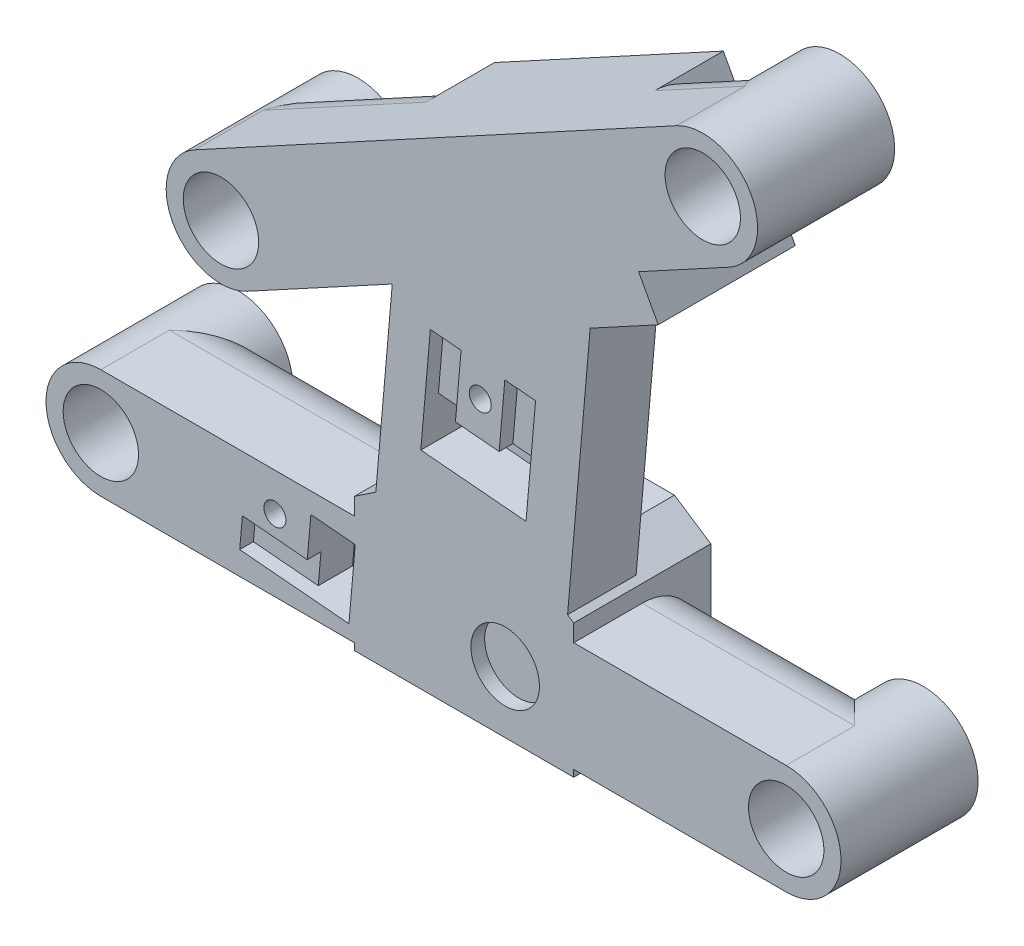
SolidWorks part; units mm, degrees
ref_plane "Front Plane" through (0, 0, 0) normal (0, 0, 1) x (1, 0, 0)
ref_plane "Top Plane" through (0, 0, 0) normal (0, 1, 0) x (1, 0, 0)
ref_plane "Right Plane" through (0, 0, 0) normal (1, 0, 0) x (0, 0, -1)
sketch "Sketch1" plane through (0, 0, 0) normal (0, 0, 1) x (1, 0, 0)
  line L0 (0, 0) -> (32, 0)
  line L1 (32, 0) -> (32, 19.5)
  line L2 (32, 19.5) -> (26.7, 23)
  line L3 (26.7, 23) -> (5.2, 23)
  line L4 (5.2, 23) -> (0, 19.5)
  line L5 (0, 19.5) -> (0, 0)
  dimension "D1" = 32
  dimension "D2" = 19.5
  dimension "D3" = 21.5
  dimension "D4" = 23
  dimension "D5" = 26.8
extrude "Boss-Extrude1" add sketch "Sketch1" along normal blind 20
sketch "Sketch2" plane through (0, 0, 0) normal (0, 0, -1) x (-1, 0, 0)
  line L0 (0, 0) -> (88.9399, 0) construction
  line L1 (88.9399, 0) -> (-120.0605, 0) construction
  line L2 (-32, 0) -> (-32, 19.5) construction
  line L3 (0, 19.5) -> (0, 0) construction
  circle A0 centre (-63, 9) radius 5.5
  circle A1 centre (-63, 9) radius 8
  circle A2 centre (37, 9) radius 5.5
  circle A3 centre (37, 9) radius 8
  dimension "D1" = 11
  dimension "D2" = 16
  dimension "D5" = 11
  dimension "D6" = 16
  dimension "D3" = 9
  dimension "D4" = 31
  dimension "D7" = 9
  dimension "D8" = 37
extrude "Boss-Extrude2" add sketch "Sketch2" against normal blind 20 separate body
sketch "Sketch4" plane through (32, 0, 0) normal (1, 0, 0) x (0, 0, -1)
  line L0 (0, 0) -> (0, 19.5) construction
  line L1 (0, 17) -> (-18, 17)
  line L2 (0, 17) -> (0, 1)
  line L3 (0, 1) -> (-18, 1)
  line L4 (-18, 17) -> (-18, 1)
  line L5 (-20, 19.5) -> (0, 19.5) construction
  dimension "D1" = 18
  dimension "D2" = 16
  dimension "D3" = 2.5
extrude "Boss-Extrude3" add sketch "Sketch4" along normal up to surface (31 mm away) up to face at (55, 9, 20)
sketch "Sketch5" plane through (0, 0, 0) normal (-1, 0, 0) x (0, 0, 1)
  line L0 (0, 19.5) -> (0, 0) construction
  line L1 (0, 17) -> (18, 17)
  line L2 (0, 17) -> (0, 1)
  line L3 (0, 1) -> (18, 1)
  line L4 (18, 17) -> (18, 1)
  line L5 (20, 19.5) -> (0, 19.5) construction
  dimension "D1" = 2.5
  dimension "D2" = 18
  dimension "D3" = 16
extrude "Boss-Extrude4" add sketch "Sketch5" along normal up to surface (37 mm away) up to face at (-45, 9, 20)
sketch "Sketch6" plane through (0, 0, 0) normal (0, 0, -1) x (-1, 0, 0)
  line L0 (-31.1, 20.0943) -> (-34.4, 57.9508)
  line L1 (-32, 19.5) -> (-26.7, 23) construction
  line L2 (-3.1254, 21.6036) -> (-5.9785, 54.3336)
  line L3 (-5.2, 23) -> (0, 19.5) construction
  line L4 (-10.9396, 45.2033) -> (-44.3289, 63.3458)
  line L5 (-44.3289, 63.3458) -> (-33.8254, 82.6765)
  line L6 (-33.8254, 82.6765) -> (-0.436, 64.5339)
  line L7 (-0.436, 64.5339) -> (-10.9396, 45.2033)
  line L8 (-32, 17) -> (-32, 19.5) construction
  line M11 (0, 19.5) -> (-5.2, 23)
  line M12 (-5.2, 23) -> (-26.7, 23)
  line M13 (-26.7, 23) -> (-32, 19.5)
  dimension "D1" = 28
  dimension "D2" = 0.9
  dimension "D3" = 38
  dimension "D4" = 2.4
  dimension "D5" = 38
  dimension "D6" = 22
  dimension "D7" = 123.5
  dimension "D8" = 11.3
extrude "Boss-Extrude5" add sketch "Sketch6" against normal blind 10 contours L2 L7 L4 L0 M13 M12 M11 region at (19.3948, 37.1745, 0)
extrude "Boss-Extrude6" add sketch "Sketch6<3>" against normal blind 20 contours L7 L6 L5 L4 region at (22.3825, 63.9399, 0)
sketch "Sketch6<3>" plane through (0, 0, 0) normal (0, 0, -1) x (-1, 0, 0) same geometry as "Sketch6"
sketch "Sketch7" plane through (0, 0, 20) normal (0, 0, 1) x (1, 0, 0)
  line L0 (-19.4685, 44.6138) -> (50.8248, 82.8087) construction
  line L3 (33.8254, 82.6765) -> (0.436, 64.5339) construction
  line L4 (0.436, 64.5339) -> (10.9396, 45.2033) construction
  line L6 (44.3289, 63.3458) -> (33.8254, 82.6765) construction
  circle A0 centre (50.8248, 82.8087) radius 5.5
  circle A1 centre (50.8248, 82.8087) radius 8
  circle A2 centre (-19.4685, 44.6138) radius 5.5
  circle A3 centre (-19.4685, 44.6138) radius 8
  dimension "D4" = 11
  dimension "D5" = 16
  dimension "D6" = 11
  dimension "D7" = 16
  dimension "D1" = 8
  dimension "D2" = 27
  dimension "D3" = 15
extrude "Boss-Extrude7" add sketch "Sketch7" against normal blind 20 separate body
sketch "Sketch8" plane through (27.409, 14.8931, 0) normal (-0.8787, -0.4774, 0) x (0, 0, 1)
  line L0 (0, 56.4956) -> (0, 44.8868) construction
  line L1 (0, 56.4956) -> (18, 56.4956)
  line L2 (0, 56.4956) -> (0, 40.4956)
  line L3 (0, 40.4956) -> (18, 40.4956)
  line L4 (18, 56.4956) -> (18, 40.4956)
  line L6 (20, 56.4956) -> (0, 56.4956) construction
  dimension "D2" = 16
  dimension "D3" = 18
extrude "Boss-Extrude8" add sketch "Sketch8" along normal up to surface (27 mm away) up to face at (-11.4685, 44.6138, 0)
sketch "Sketch9" plane through (60.7984, 33.0356, 0) normal (0.8787, 0.4774, 0) x (0, 0, -1)
  line L1 (0, 56.4956) -> (-18, 56.4956)
  line L2 (0, 56.4956) -> (0, 40.4956)
  line L3 (0, 40.4956) -> (-18, 40.4956)
  line L4 (-18, 56.4956) -> (-18, 40.4956)
  dimension "D1" = 18
  dimension "D2" = 16
extrude "Boss-Extrude9" add sketch "Sketch9" along normal up to surface (15 mm away) up to face at (58.8248, 82.8087, 0)
fillet "Fillet1" radius 8 8 edges at (47.5, 1, 18) (47.5, 17, 18) (48.0543, 72.1986, 18) (40.4154, 86.2572, 18) (-11.426, 58.0885, 18) (-3.787, 44.0299, 18) (-18.5, 1, 18) (-18.5, 17, 18)
sketch "Sketch10" plane through (0, 0, 20) normal (0, 0, 1) x (1, 0, 0)
  line L0 (9.0299, 48.7179) -> (42.4192, 66.8605)
  line L1 (0.436, 64.5339) -> (10.9396, 45.2033) construction
  line L2 (44.3289, 63.3458) -> (33.8254, 82.6765) construction
  line L3 (42.4192, 66.8605) -> (41.4643, 68.6178)
  line L4 (41.4643, 68.6178) -> (8.075, 50.4753)
  line L5 (8.075, 50.4753) -> (10.9396, 45.2033) construction
  line L6 (8.075, 50.4753) -> (9.0299, 48.7179)
  line L8 (10.9396, 45.2033) -> (44.3289, 63.3458) construction
  dimension "D1" = 2
  dimension "D2" = 4
extrude "Cut-Extrude1" cut sketch "Sketch10" against normal blind 1
sketch "Sketch11" plane through (0, 0, 20) normal (0, 0, 1) x (1, 0, 0)
  line L0 (18.9906, 10.8834) -> (18.6, 6.3)
  line L1 (18.6, 6.3) -> (8.0383, 7.2)
  line L2 (8.0383, 7.2) -> (8.4288, 11.7834)
  line L3 (8.4288, 11.7834) -> (18.9906, 10.8834)
  line L4 (0, 0) -> (32, 0) construction
  line L5 (32, 0) -> (32, 19.5) construction
  dimension "D1" = 10.6
  dimension "D2" = 4.6
  dimension "D3" = 6.3
  dimension "D4" = 7.2
  dimension "D5" = 13.4
extrude "Boss-Extrude10" add sketch "Sketch11" along normal blind 2.8
sketch "Sketch12" plane through (0, 0, 0) normal (0, 0, -1) x (-1, 0, 0)
  line L0 (-31.1, 20.0943) -> (-3.2058, 22.5259) construction
  line L1 (-3.1254, 21.6036) -> (-5.5212, 49.0876) construction
  line L2 (-25.0378, 28.8539) -> (-9.6901, 30.1918)
  line L3 (-9.6901, 30.1918) -> (-11.0796, 46.1313)
  line L4 (-11.0796, 46.1313) -> (-15.5626, 45.7405)
  line L5 (-15.5626, 45.7405) -> (-14.7376, 36.2764)
  line L6 (-14.7376, 36.2764) -> (-21.1193, 35.7201)
  line L7 (-21.1193, 35.7201) -> (-21.9443, 45.1842)
  line L8 (-21.9443, 45.1842) -> (-26.4273, 44.7934)
  line L9 (-26.4273, 44.7934) -> (-25.0378, 28.8539)
  line L10 (-25.6023, 35.3293) -> (-10.2546, 36.6672)
  line L11 (-31.1, 20.0943) -> (-34.4, 57.9508) construction
  line L12 (-17.9284, 35.9983) -> (-19.3449, 52.248) construction
  line L13 (0, 0) -> (-32, 0) construction
  line L14 (-32, 0) -> (-32, 1) construction
  line L15 (-0.1188, 13.4597) -> (0.8, 3)
  line L16 (0.8, 3) -> (16.7386, 4.4)
  line L17 (16.7386, 4.4) -> (16.3449, 8.8827)
  line L18 (16.3449, 8.8827) -> (6.8813, 8.0515)
  line L19 (6.8813, 8.0515) -> (6.3563, 14.0285)
  line L20 (6.3563, 14.0285) -> (-0.1188, 13.4597)
  line L21 (6.8813, 8.0515) -> (7.2751, 3.5688)
  line L22 (37, 1) -> (0, 1) construction
  line L23 (0, 1) -> (0, 0) construction
  line L24 (6.8813, 8.0515) -> (7.2751, 3.5688)
  circle A0 centre (-18.3626, 40.9794) radius 1.6
  circle A1 centre (-22, 9) radius 5
  circle A2 centre (11.5996, 11.4775) radius 1.605
  dimension "D7" = 3.2
  dimension "D9" = 10
  dimension "D12" = 3.21
  dimension "D1" = 8.2
  dimension "D2" = 6.8
  dimension "D3" = 5.7941
  dimension "D4" = 4.5
  dimension "D5" = 16
  dimension "D6" = 9.5
  dimension "D8" = 5
  dimension "D10" = 9
  dimension "D11" = 10
  dimension "D13" = 16
  dimension "D14" = 10.5
  dimension "D15" = 6.5
  dimension "D16" = 6
  dimension "D17" = 3
  dimension "D18" = 5
  dimension "D19" = 2
  dimension "D20" = 0.8
  dimension "D21" = 3.4
extrude "Cut-Extrude2" cut sketch "Sketch12" against normal blind 2 contours A1 region at (22, 9, 0)
extrude "Cut-Extrude3" cut sketch "Sketch12<4>" against normal blind 7 contours L21 L19 L20 L15 L16 | L10 L9 L2 L3 L6 region at (17.6462, 32.7605, 0) region at (-3.5782, 8.5142, 0)
sketch "Sketch12<4>" plane through (0, 0, 0) normal (0, 0, -1) x (-1, 0, 0) same geometry as "Sketch12"
extrude "Cut-Extrude4" cut sketch "Sketch12<6>" against normal blind 2 contours L18 L21 L16 L17 | L5 L10 L3 L4 | L9 L10 L7 L8 region at (23.7733, 40.2568, 0) region at (12.9086, 41.2039, 0) region at (-11.81, 6.2257, 0)
sketch "Sketch12<6>" plane through (0, 0, 0) normal (0, 0, -1) x (-1, 0, 0) same geometry as "Sketch12"
extrude "Cut-Extrude5" cut sketch "Sketch12<7>" against normal blind 8 contours A2 | A0 region at (18.3626, 40.9794, 0) region at (-11.5996, 11.4775, 0)
sketch "Sketch12<7>" plane through (0, 0, 0) normal (0, 0, -1) x (-1, 0, 0) same geometry as "Sketch12"
sketch "Sketch13" plane through (1.2328, -0.1075, 0) normal (-0.9962, 0.0868, 0) x (0, 0, 1)
  line L0 (0, 21.7934) -> (0, 49.3816) construction
  line L1 (4.2, 45.2934) -> (7, 45.2934)
  line L2 (4.2, 45.2934) -> (4.2, 39.4934)
  line L3 (4.2, 39.4934) -> (7, 39.4934)
  line L4 (7, 45.2934) -> (7, 39.4934)
  line L5 (10, 21.7934) -> (0, 21.7934) construction
  dimension "D1" = 5.8
  dimension "D2" = 2.8
  dimension "D3" = 4.2
  dimension "D4" = 17.7
extrude "Cut-Extrude6" cut sketch "Sketch13" against normal blind 22
sketch "Sketch14" plane through (0, 1, 0) normal (0, -1, 0) x (1, 0, 0)
  line L0 (0, 0) -> (0, 10) construction
  line L1 (-15.4, 7) -> (-9.6, 7)
  line L2 (-15.4, 7) -> (-15.4, 4.2)
  line L3 (-15.4, 4.2) -> (-9.6, 4.2)
  line L4 (-9.6, 7) -> (-9.6, 4.2)
  line L5 (-37, 0) -> (0, 0) construction
  dimension "D1" = 5.8
  dimension "D2" = 2.8
  dimension "D3" = 9.6
  dimension "D4" = 4.2
extrude "Cut-Extrude7" cut sketch "Sketch14" against normal blind 14.5
mirror "Mirror8" about plane through (50.8248, 82.8087, 0) normal (0, 0, 1) of "Boss-Extrude1"
mirror "Mirror10" about plane through (50.8248, 82.8087, 0) normal (0, 0, 1) of "Boss-Extrude3", "Boss-Extrude4", "Boss-Extrude5", "Boss-Extrude6", "Boss-Extrude8", "Boss-Extrude9", "Fillet1", "Cut-Extrude1", "Boss-Extrude10", "Cut-Extrude2", "Cut-Extrude3", "Cut-Extrude4", "Cut-Extrude5", "Cut-Extrude6", "Cut-Extrude7"
sketch "Sketch15" plane through (0, 0, 0) normal (0, 0, -1) x (-1, 0, 0)
  circle A0 centre (-50.8248, 82.8087) radius 5.5
  circle A1 centre (-50.8248, 82.8087) radius 8
  circle A2 centre (19.4685, 44.6138) radius 5.5
  circle A3 centre (19.4685, 44.6138) radius 8
  circle A4 centre (37, 9) radius 5.5
  circle A5 centre (37, 9) radius 8
  circle A6 centre (-63, 9) radius 5.5
  circle A7 centre (-63, 9) radius 8
  dimension "D1" = 11
  dimension "D2" = 16
extrude "Boss-Extrude11" add sketch "Sketch15" along normal blind 20
sketch "Sketch16" plane through (-26.973, 49.6409, 0) normal (-0.4774, 0.8787, 0) x (0.8787, 0.4774, 0)
  line L0 (0, 0) -> (-59.1276, 0)
  line L1 (-59.1276, 0) -> (-59.1276, -32.6264)
  line L2 (-59.1276, -32.6264) -> (114.1765, -32.6264)
  line L3 (114.1765, -32.6264) -> (114.1765, 0)
  line L4 (114.1765, 0) -> (0, 0)
extrude "Cut-Extrude8" cut sketch "Sketch16" against normal through all both and the other way through all
sketch "Sketch17" plane through (0, 1, 0) normal (0, -1, 0) x (1, 0, 0)
  line L0 (-9.6, -4.2) -> (-8.1, -4.2)
  line L1 (-8.1, -4.2) -> (-8.1, -7)
  line L2 (-8.1, -7) -> (-9.6, -7)
  line L3 (-9.6, -4.2) -> (-9.6, -7)
  dimension "D1" = 1.5
extrude "Cut-Extrude10" cut sketch "Sketch17" against normal up to surface (14.5 mm away) up to face at (-12.5, 15.5, -5.6)
